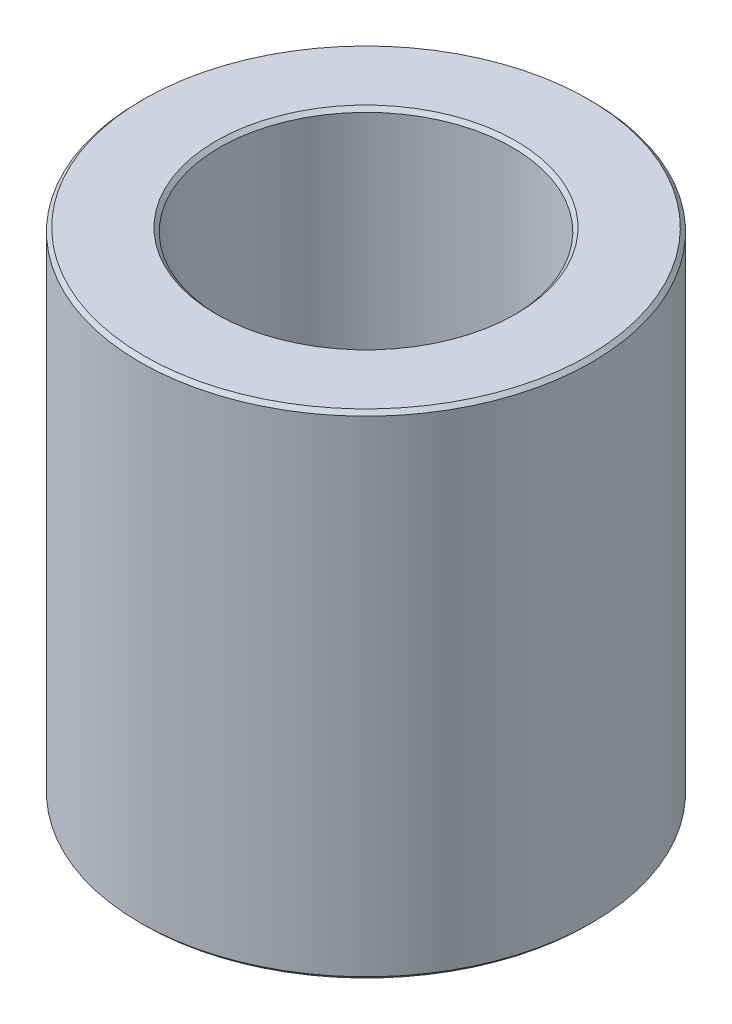
SolidWorks part; units mm, degrees
ref_plane "Front Plane" through (0, 0, 0) normal (0, 0, 1) x (1, 0, 0)
ref_plane "Top Plane" through (0, 0, 0) normal (0, 1, 0) x (1, 0, 0)
ref_plane "Right Plane" through (0, 0, 0) normal (1, 0, 0) x (0, 0, -1)
sketch "Sketch1" plane through (0, 0, 0) normal (0, 1, 0) x (1, 0, 0)
  circle A0 centre (0, 0) radius 27.5
  dimension "SLEEVE_OD" = 55
extrude "Boss-Extrude1" add sketch "Sketch1" along normal blind 59.986
sketch "Sketch2" plane through (0, 0, 0) normal (0, 1, 0) x (1, 0, 0)
  circle A0 centre (0, 0) radius 17.7992
  dimension "BORE_D" = 35.5983
extrude "Cut-Extrude1" cut sketch "Sketch2" along normal through all
chamfer "Chamfer1" distance 0.4506 angle 45 4 edges at (0, 59.986, 17.7992) (0, 0, 17.7992) (0, 0, 27.5) (0, 59.986, 27.5)
